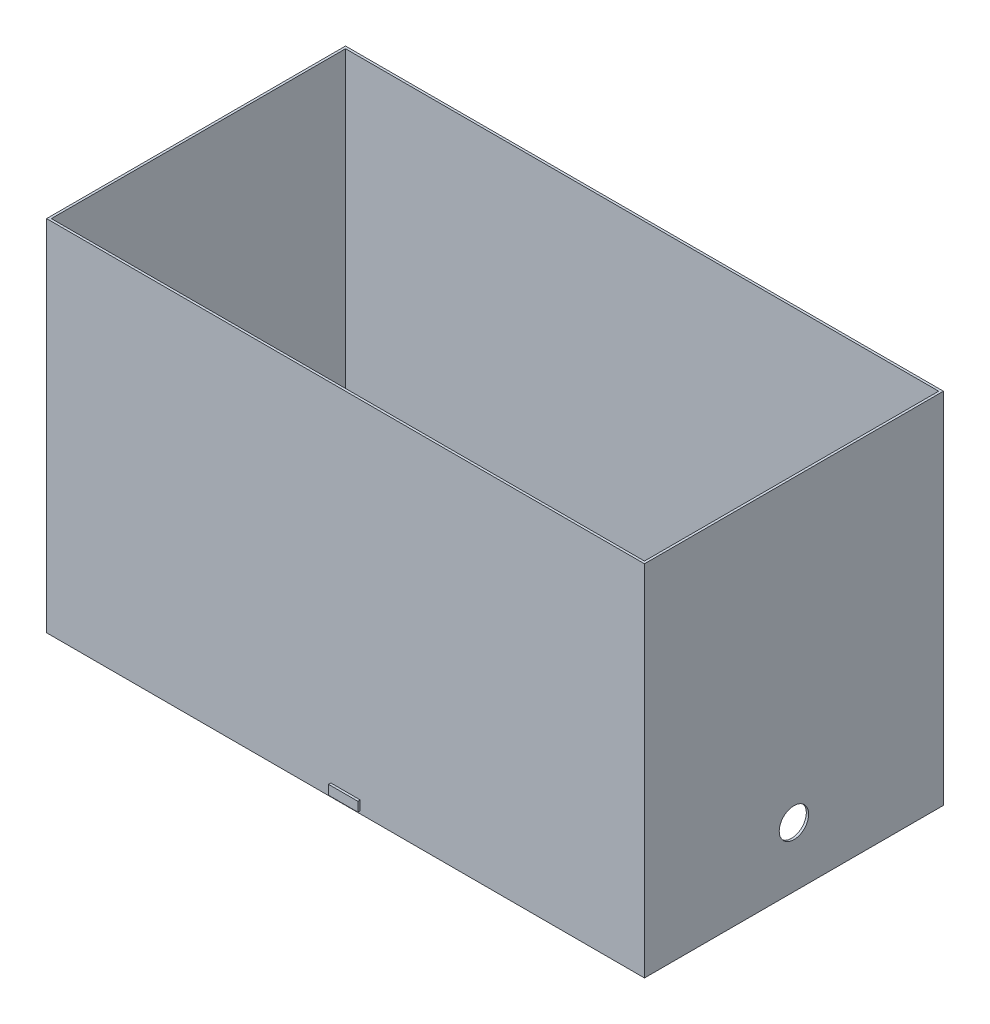
SolidWorks part; units mm, degrees
ref_plane "Front Plane" through (0, 0, 0) normal (0, 0, 1) x (1, 0, 0)
ref_plane "Top Plane" through (0, 0, 0) normal (0, 1, 0) x (1, 0, 0)
ref_plane "Right Plane" through (0, 0, 0) normal (1, 0, 0) x (0, 0, -1)
sketch "Sketch1" plane through (0, 0, 0) normal (0, 1, 0) x (1, 0, 0)
  line L0 (-252, 125) -> (252, 125)
  line L1 (-254, -127) -> (254, -127)
  line L2 (-254, -127) -> (-254, 127)
  line L3 (-254, 127) -> (254, 127)
  line L4 (254, -127) -> (254, 127)
  line L5 (-254, -127) -> (254, 127) construction
  line L6 (-254, 127) -> (254, -127) construction
  line L7 (252, -125) -> (252, 125)
  line L8 (-252, -125) -> (252, -125)
  line L9 (-252, -125) -> (-252, 125)
  point P0 (0, 0)
  dimension "D1" = 254
  dimension "D2" = 508
  dimension "D3" = 2
extrude "Boss-Extrude1" add sketch "Sketch1" along normal blind 304.8
sketch "Sketch2" plane through (-254, 0, 0) normal (-1, 0, 0) x (0, 0, 1)
  line L0 (0, 50.8) -> (0, 0) construction
  line L1 (-127, 0) -> (127, 0) construction
  circle A0 centre (0, 50.8) radius 12.5
  dimension "D1" = 50.8
  dimension "D2" = 25
extrude "Cut-Extrude1" cut sketch "Sketch2" against normal through all
sketch "Sketch3" plane through (0, 0, 127) normal (0, 0, 1) x (1, 0, 0)
  line L0 (-12.5, 10.2785) -> (12.5, 10.2785)
  line L1 (-12.5, 10.2785) -> (12.5, 2.2785) construction
  line L2 (-12.5, 2.2785) -> (12.5, 10.2785) construction
  line L3 (0, 6.2785) -> (0, 0) construction
  line L4 (-254, 0) -> (254, 0) construction
  line L5 (-12.5, 10.2785) -> (-12.5, 2.2785)
  line L6 (-12.5, 2.2785) -> (12.5, 2.2785)
  line L7 (12.5, 10.2785) -> (12.5, 2.2785)
  dimension "D1" = 25
  dimension "D2" = 8
extrude "Boss-Extrude2" add sketch "Sketch3" along normal blind 2
